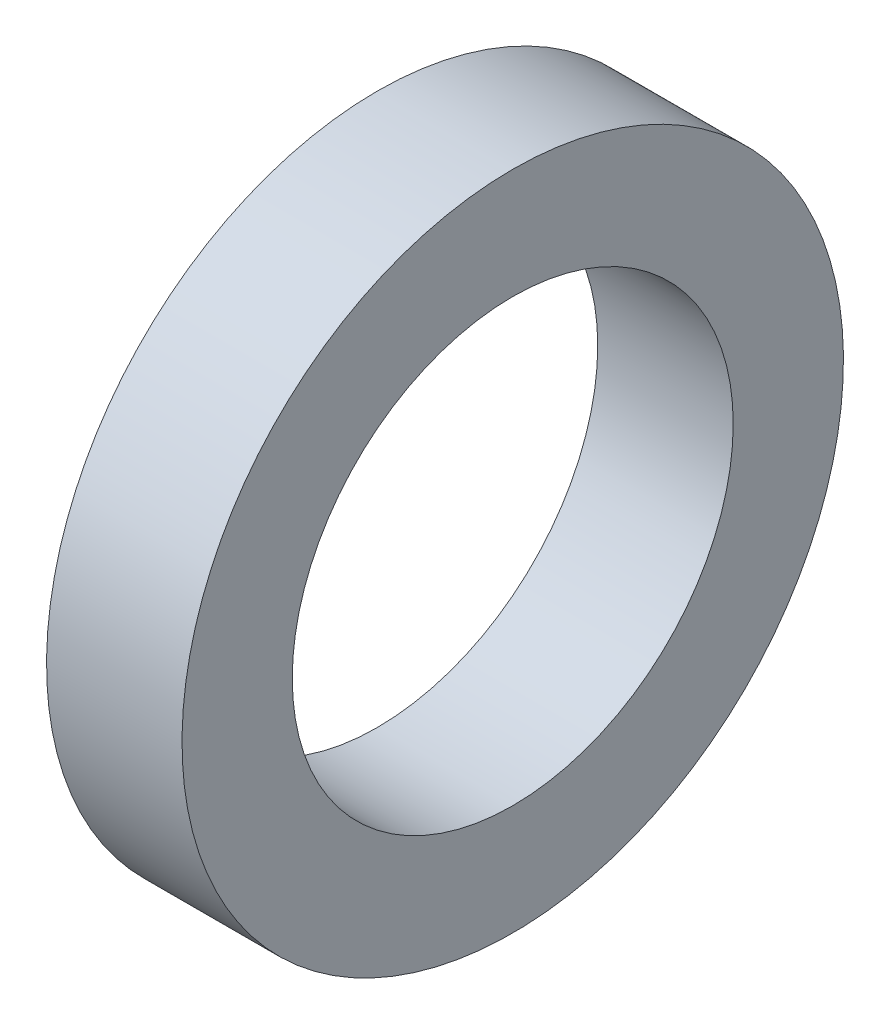
SolidWorks part; units mm, degrees
ref_plane "Front Plane" through (0, 0, 0) normal (0, 0, 1) x (1, 0, 0)
ref_plane "Top Plane" through (0, 0, 0) normal (0, 1, 0) x (1, 0, 0)
ref_plane "Right Plane" through (0, 0, 0) normal (1, 0, 0) x (0, 0, -1)
sketch "Sketch1" plane through (0, 0, 0) normal (0, 0, 1) x (1, 0, 0)
  line L0 (0, 0) -> (0, 9.525)
  line L1 (0, 9.525) -> (3.9014, 9.525)
  line L2 (3.9014, 9.525) -> (3.9014, 6.35)
  line L3 (3.9014, 6.35) -> (3.9014, 0)
  line L4 (3.9014, 0) -> (0, 0)
  line L5 (3.9014, 6.35) -> (0, 6.35)
  dimension "D1" = 3.9014
  dimension "D2" = 9.525
  dimension "D3" = 6.35
revolve "Revolve1" add sketch "Sketch1" angle 360 about L4 region at (1.9507, 7.9375, 0)
